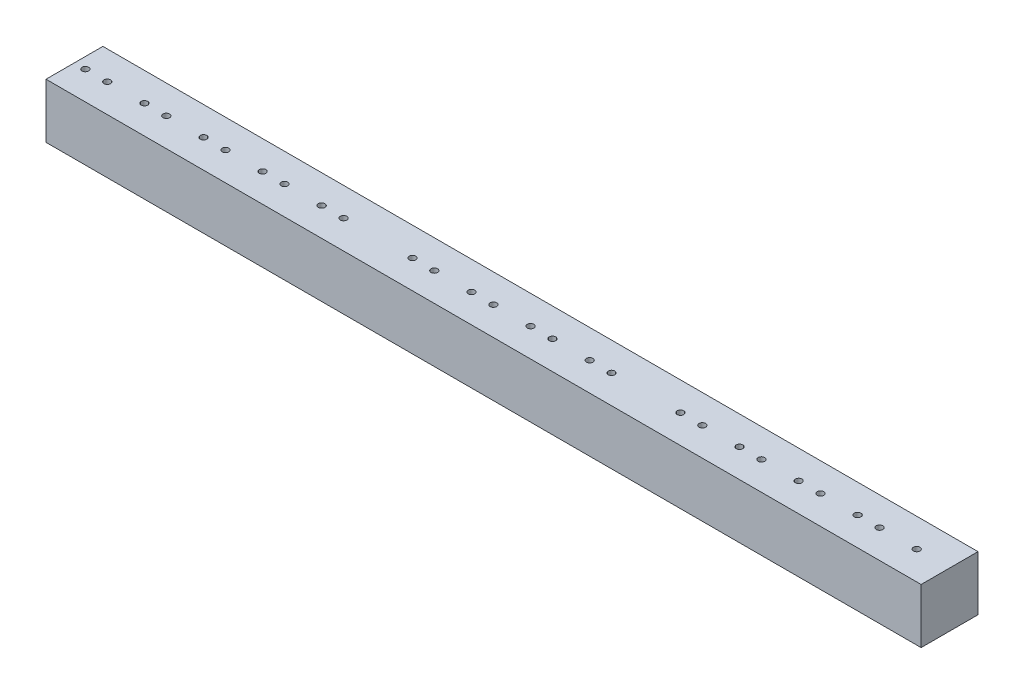
SolidWorks part; units mm, degrees
ref_plane "Front Plane" through (0, 0, 0) normal (0, 0, 1) x (1, 0, 0)
ref_plane "Top Plane" through (0, 0, 0) normal (0, 1, 0) x (1, 0, 0)
ref_plane "Right Plane" through (0, 0, 0) normal (1, 0, 0) x (0, 0, -1)
sketch "Belt Drive Axle" plane through (0, 0, 0) normal (0, 1, 0) x (1, 0, 0)
  line L0 (-48.26, 3.302) -> (-48.26, -3.1369) construction
  line L1 (-50.8, -3.302) -> (50.8, -3.302)
  line L2 (-50.8, -3.302) -> (-50.8, 3.302)
  line L3 (-50.8, 3.302) -> (50.8, 3.302)
  line L4 (50.8, -3.302) -> (50.8, 3.302)
  line L5 (-50.8, -3.302) -> (50.8, 3.302) construction
  line L6 (-50.8, 3.302) -> (50.8, -3.302) construction
  line L7 (-41.402, 3.302) -> (-41.402, -3.302) construction
  line L8 (-50.8, 0) -> (50.8, 0) construction
  line L9 (-41.402, 3.302) -> (-41.402, -3.1369) construction
  line L10 (-34.544, 3.302) -> (-34.544, -3.1369) construction
  line L11 (-27.686, 3.302) -> (-27.686, -3.1369) construction
  line L12 (-20.828, 3.302) -> (-20.828, -3.1369) construction
  line L13 (0, 3.302) -> (0, -3.302) construction
  line L14 (-3.429, 3.302) -> (-3.429, -3.302) construction
  line L15 (-10.287, 3.302) -> (-10.287, -3.302) construction
  line L16 (10.287, 3.302) -> (10.287, -3.302) construction
  line L17 (3.429, 3.302) -> (3.429, -3.302) construction
  line L18 (20.828, 3.302) -> (20.828, -3.1369) construction
  line L19 (27.686, 3.302) -> (27.686, -3.1369) construction
  line L20 (34.544, 3.302) -> (34.544, -3.1369) construction
  line L21 (41.402, 3.302) -> (41.402, -3.1369) construction
  line L22 (41.402, 3.302) -> (41.402, -3.302) construction
  line L23 (48.26, 3.302) -> (48.26, -3.1369) construction
  circle A0 centre (-49.53, 0) radius 0.381
  circle A1 centre (-46.99, 0) radius 0.381
  circle A2 centre (-42.672, 0) radius 0.381
  circle A3 centre (-40.132, 0) radius 0.381
  circle A4 centre (-35.814, 0) radius 0.381
  circle A5 centre (-33.274, 0) radius 0.381
  circle A6 centre (-28.956, 0) radius 0.381
  circle A7 centre (-26.416, 0) radius 0.381
  circle A8 centre (-22.098, 0) radius 0.381
  circle A9 centre (-19.558, 0) radius 0.381
  circle A10 centre (-4.699, 0) radius 0.381
  circle A11 centre (-2.159, 0) radius 0.381
  circle A12 centre (-9.017, 0) radius 0.381
  circle A13 centre (-11.557, 0) radius 0.381
  circle A14 centre (11.557, 0) radius 0.381
  circle A15 centre (9.017, 0) radius 0.381
  circle A16 centre (2.159, 0) radius 0.381
  circle A17 centre (4.699, 0) radius 0.381
  circle A18 centre (19.558, 0) radius 0.381
  circle A19 centre (22.098, 0) radius 0.381
  circle A20 centre (26.416, 0) radius 0.381
  circle A21 centre (28.956, 0) radius 0.381
  circle A22 centre (33.274, 0) radius 0.381
  circle A23 centre (35.814, 0) radius 0.381
  circle A24 centre (40.132, 0) radius 0.381
  circle A25 centre (42.672, 0) radius 0.381
  circle A26 centre (46.99, 0) radius 0.381
  point P0 (0, 0)
  dimension "D5" = 0.762
  dimension "D6" = 1.27
  dimension "D9" = 0.762
  dimension "D10" = 1.27
  dimension "D12" = 0.762
  dimension "D1" = 6.604
  dimension "D2" = 101.6
  dimension "D3" = 1.27
  dimension "D4" = 6.858
  dimension "D8" = 3.429
  dimension "D11" = 6.858
  dimension "D13" = 1.27
  dimension "D7" = 5
extrude "Boss-Extrude1" add sketch "Belt Drive Axle" along normal blind 6.35
equation "\"Ball Diameter\"= 1.75in"
equation "\"Sheet Thickness\"= 0.25in"
equation "\"Screw Diameter\"= .17in"
equation "\"Robot Diameter\"= 14in"
equation "\"Castor Screw Diameter\"= 0.22in"
equation "\"Wheel Diameter\" = 4in"
equation "\"Nut Diameter\" = 8.4mm"
equation "\"Nut Height\" = 2.9mm"
equation "\"Screw Height\" = 0.55in"
equation "\"Pulley Diameter\" = 1in"
equation "\"Reactor Height\" = 14in"
equation "\"Elevator Height\" = 11.5in"
equation "\"Elevator Width\" = \"Ball Diameter\" + 0.25in"
equation "\"Elevator Axle Length\" = \"Elevator Width\" + 8*\"Sheet Thickness\""
equation "\"D2@Belt Drive Axle\"=\"Elevator Axle Length\""
equation "\"D1@Boss-Extrude1\"=\"Sheet Thickness\""
